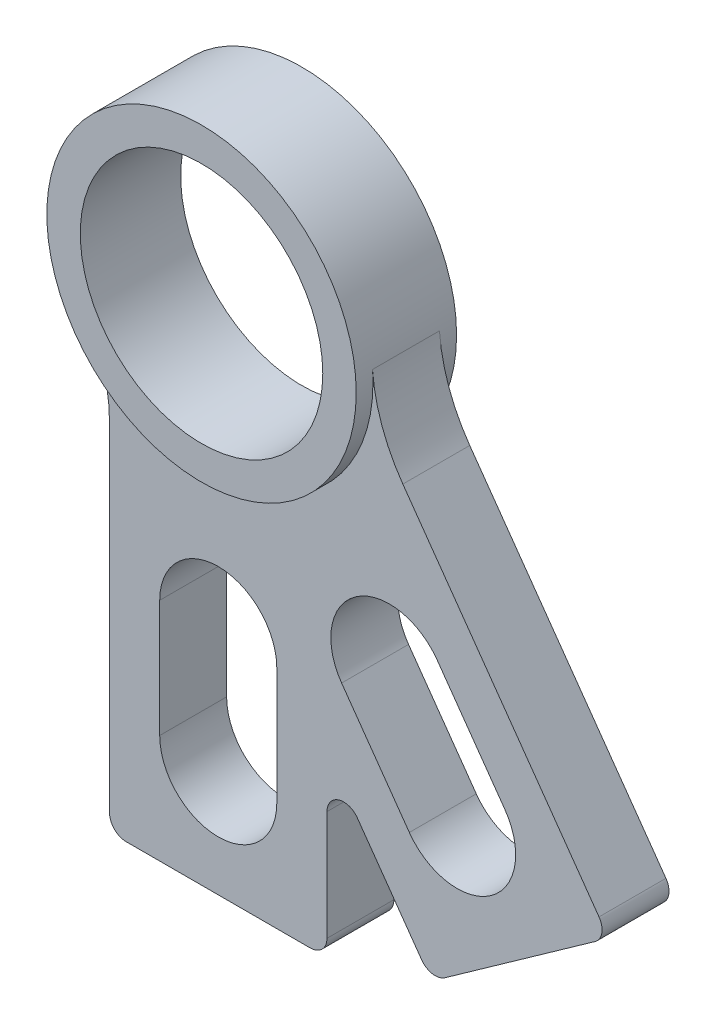
SolidWorks part; units mm, degrees
material "AISI 4130 Steel, annealed at 865C"
ref_plane "X-Y Datum" through (0, 0, 0) normal (0, 0, 1) x (1, 0, 0)
ref_plane "X-Z Datum" through (0, 0, 0) normal (0, 1, 0) x (1, 0, 0)
ref_plane "Y-Z Datum" through (0, 0, 0) normal (1, 0, 0) x (0, 0, -1)
sketch "Sketch1" plane through (0, 0, 0) normal (0, 0, 1) x (1, 0, 0)
  line L0 (0, -39.0706) -> (0, -27.9581) construction
  line L1 (-5.5562, -39.0706) -> (-5.5562, -27.9581)
  line L2 (5.5562, -39.0706) -> (5.5562, -27.9581)
  line L3 (22.6674, -31.9787) -> (16.2412, -22.9128) construction
  line L4 (18.1344, -35.1918) -> (11.7082, -26.1259)
  line L5 (27.2003, -28.7657) -> (20.7742, -19.6997)
  line L6 (-10.3187, -15.7343) -> (-10.3187, -49.3893)
  line L7 (-10.3187, -49.3893) -> (10.3187, -49.3893)
  line L10 (20.2161, -46.3643) -> (37.0529, -34.43)
  line L11 (37.0529, -34.43) -> (17.5173, -6.8694)
  line L12 (0, -39.0706) -> (0, 0) construction
  line L13 (0, 0) -> (22.6674, -31.9787) construction
  line L14 (0, -44.6268) -> (0, -49.3893) construction
  line L15 (25.8805, -36.5117) -> (28.6345, -40.3971) construction
  line L16 (23.9872, -24.2327) -> (27.8727, -21.4786) construction
  line L17 (-5.5562, -33.5143) -> (-10.3187, -33.5143) construction
  line L18 (-10.3187, -17.6393) -> (10.3187, -17.6393) construction
  line L19 (10.3187, -17.6393) -> (10.3187, -49.3893) construction
  line L20 (5.5562, -33.5143) -> (10.3187, -33.5143) construction
  line L21 (0, -22.4018) -> (0, -17.6393) construction
  line L22 (20.2161, -46.3643) -> (1.8556, -20.4616) construction
  line L23 (1.8556, -20.4616) -> (18.6924, -8.5272) construction
  line L24 (14.9213, -30.6589) -> (11.0359, -33.4129) construction
  line L25 (13.0281, -18.3798) -> (10.274, -14.4944) construction
  line L30 (20.2161, -46.3643) -> (10.3187, -32.4012)
  line L32 (10.3187, -32.4012) -> (10.3187, -49.3893)
  circle A0 centre (0, 0) radius 11.5062
  arc A1 (-5.5562, -39.0706) -> (5.5562, -39.0706) centre (0, -39.0706) ccw
  arc A2 (5.5562, -27.9581) -> (-5.5562, -27.9581) centre (0, -27.9581) ccw
  arc A3 (18.1344, -35.1918) -> (27.2003, -28.7657) centre (22.6674, -31.9787) ccw
  arc A4 (20.7742, -19.6997) -> (11.7082, -26.1259) centre (16.2412, -22.9128) ccw
  arc A5 (14.6392, 1.1103) -> (-12.5852, -7.5598) centre (0, 0) ccw
  arc A6 (17.5173, -6.8694) -> (14.6392, 1.1103) centre (30.4687, 2.3108) cw
  arc A7 (-10.3187, -15.7343) -> (-12.5852, -7.5598) centre (-26.1937, -15.7343) ccw
  arc A14 (-12.5852, -7.5598) -> (14.6392, 1.1103) centre (0, 0) ccw
  point P5 (0, -33.5143)
  point P11 (19.4543, -27.4458)
  point P24 (28.6345, -40.3971)
  point P31 (0, -49.3893)
  point P39 (25.8805, -36.5117)
  dimension "D1" = 23.0124
  dimension "D2" = 14.6812
  dimension "D8" = 15.875
  dimension "D9" = 35.33
  dimension "D3" = 20.6375
  dimension "D4" = 4.7625
  dimension "D5" = 31.75
  dimension "D6" = 2.032
  dimension "D7" = 1.905
extrude "Boss-Extrude1" add sketch "Sketch1" along normal blind 4.7625 and the other way blind 4.7625 contours A5 A14 A0 | A14 A7 L6 L7 L32 L30 L10 L11 A6 A4 L5 A3 L4 A2 L2 A1 L1 region at (9.1425, -28.5984, 0) region at (-4.329, 13.5933, 0)
sketch "Sketch2" plane through (0, 0, 0) normal (0, 0, 1) x (1, 0, 0)
  line L0 (0, -39.0706) -> (0, -27.9581) construction
  line L1 (-5.5562, -39.0706) -> (-5.5562, -27.9581)
  line L2 (5.5562, -39.0706) -> (5.5562, -27.9581)
  line L3 (22.6674, -31.9787) -> (16.2412, -22.9128) construction
  line L4 (18.1344, -35.1918) -> (11.7082, -26.1259)
  line L5 (27.2003, -28.7657) -> (20.7742, -19.6997)
  line L6 (-10.3187, -15.7343) -> (-10.3187, -49.3893)
  line L7 (-10.3187, -49.3893) -> (10.3187, -49.3893)
  line L10 (20.2161, -46.3643) -> (37.0529, -34.43)
  line L11 (37.0529, -34.43) -> (17.5173, -6.8694)
  line L12 (0, -39.0706) -> (0, 0) construction
  line L13 (0, 0) -> (22.6674, -31.9787) construction
  line L14 (0, -44.6268) -> (0, -49.3893) construction
  line L15 (25.8805, -36.5117) -> (28.6345, -40.3971) construction
  line L16 (23.9872, -24.2327) -> (27.8727, -21.4786) construction
  line L17 (-5.5562, -33.5143) -> (-10.3187, -33.5143) construction
  line L18 (-10.3187, -17.6393) -> (10.3187, -17.6393) construction
  line L19 (10.3187, -17.6393) -> (10.3187, -49.3893) construction
  line L20 (5.5562, -33.5143) -> (10.3187, -33.5143) construction
  line L21 (0, -22.4018) -> (0, -17.6393) construction
  line L22 (20.2161, -46.3643) -> (1.8556, -20.4616) construction
  line L23 (1.8556, -20.4616) -> (18.6924, -8.5272) construction
  line L24 (14.9213, -30.6589) -> (11.0359, -33.4129) construction
  line L25 (13.0281, -18.3798) -> (10.274, -14.4944) construction
  line L30 (20.2161, -46.3643) -> (10.3187, -32.4012)
  line L32 (10.3187, -32.4012) -> (10.3187, -49.3893)
  arc A1 (-5.5562, -39.0706) -> (5.5562, -39.0706) centre (0, -39.0706) ccw
  arc A2 (5.5562, -27.9581) -> (-5.5562, -27.9581) centre (0, -27.9581) ccw
  arc A3 (18.1344, -35.1918) -> (27.2003, -28.7657) centre (22.6674, -31.9787) ccw
  arc A4 (20.7742, -19.6997) -> (11.7082, -26.1259) centre (16.2412, -22.9128) ccw
  arc A6 (17.5173, -6.8694) -> (14.6392, 1.1103) centre (30.4687, 2.3108) cw
  arc A7 (-10.3187, -15.7343) -> (-12.5852, -7.5598) centre (-26.1937, -15.7343) ccw
  arc A14 (-12.5852, -7.5598) -> (14.6392, 1.1103) centre (0, 0) ccw
  point P5 (0, -33.5143)
  point P11 (19.4543, -27.4458)
  point P24 (28.6345, -40.3971)
  point P31 (0, -49.3893)
  point P39 (25.8805, -36.5117)
  dimension "D1" = 7.5598
  dimension "D2" = 14.6812
  dimension "D8" = 15.875
  dimension "D9" = 35.33
  dimension "D3" = 20.6375
  dimension "D4" = 4.7625
  dimension "D5" = 31.75
  dimension "D6" = 2.032
  dimension "D7" = 1.905
extrude "Cut-Extrude1" cut sketch "Sketch2" along normal blind 1.5875 from surface starting at face at (11.5062, 0, -4.7625)
extrude "Cut-Extrude2" cut sketch "Sketch2<6>" against normal blind 1.5875 from surface starting at face at (11.5062, 0, 4.7625)
sketch "Sketch2<6>" plane through (0, 0, 0) normal (0, 0, 1) x (1, 0, 0) same geometry as "Sketch2"
fillet "Fillet1" radius 1.5875 5 edges at (37.0529, -34.43, 0) (20.2161, -46.3643, 0) (10.3187, -49.3893, 0) (-10.3187, -49.3893, 0) (10.3187, -32.4012, 0)
sketch "Sketch3" plane through (0, 0, 4.7625) normal (0, 0, 1) x (1, 0, 0)
  point P0 (0, 0)
sketch "Sketch4" plane through (0, 0, -4.7625) normal (0, 0, -1) x (-1, 0, 0)
  point P0 (0, 0)
